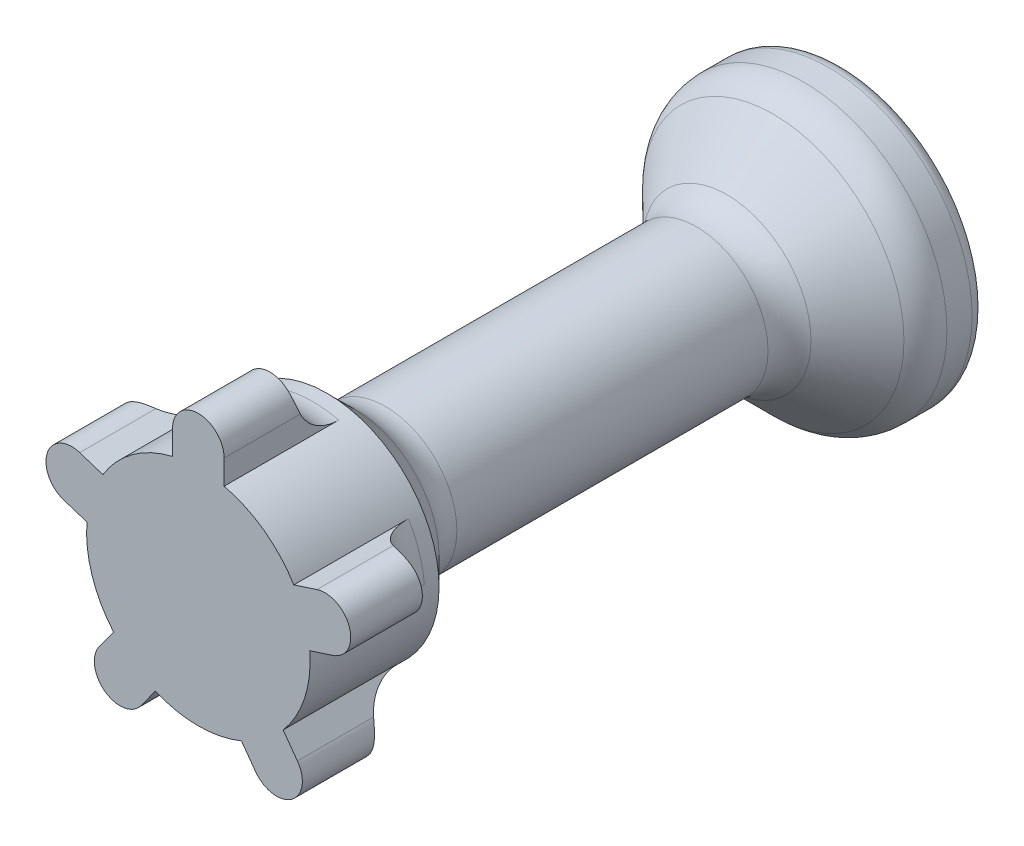
SolidWorks part; units mm, degrees
note: '?' marks a value the reader was unsure of.
ref_plane "Front Plane" through (0, 0, 0) normal (0, 0, 1) x (1, 0, 0)
ref_plane "Top Plane" through (0, 0, 0) normal (0, 1, 0) x (1, 0, 0)
ref_plane "Right Plane" through (0, 0, 0) normal (1, 0, 0) x (0, 0, -1)
ref_axis "Center_Axis" through (0, 0, -88.99) along (0, 0, 1)?
sketch "Sketch1" plane through (0, 0, 0) normal (0, 0, 1) x (1, 0, 0)
  line L0 (11.9266, 1.4716) -> (9.8733, 0.8044)
  line L1 (10.5138, 5.8198) -> (8.4605, 5.1526)
  line L2 (5.0851, -10.8882) -> (3.816, -9.1415)
  line L3 (8.7839, -8.2008) -> (7.5149, -6.4541)
  line L6 (-8.7839, -8.2008) -> (-7.5149, -6.4541)
  line L8 (-2.286, 11.7976) -> (-2.286, 9.6386)
  line L9 (2.286, 11.7976) -> (2.286, 9.6386)
  line L10 (-5.0851, -10.8882) -> (-3.816, -9.1415)
  line L11 (-10.5138, 5.8198) -> (-8.4605, 5.1526)
  line L12 (-11.9266, 1.4716) -> (-9.8733, 0.8044)
  circle A1 centre (0, 0) radius 9.906
  arc A3 (-2.286, 11.7976) -> (2.286, 11.7976) centre (0, 11.7976) cw
  arc A4 (10.5138, 5.8198) -> (11.9266, 1.4716) centre (11.2202, 3.6457) cw
  arc A5 (8.7839, -8.2008) -> (5.0851, -10.8882) centre (6.9345, -9.5445) cw
  arc A6 (-5.0851, -10.8882) -> (-8.7839, -8.2008) centre (-6.9345, -9.5445) cw
  arc A7 (-11.9266, 1.4716) -> (-10.5138, 5.8198) centre (-11.2202, 3.6457) cw
  point P14 (0, 0)
  point P30 (0, 0)
  dimension "D1" = 5
  dimension "D3" = 19.812
  dimension "D5" = 2.159
  dimension "D6" = 4.572
extrude "Boss-Extrude1" add sketch "Sketch1" along normal blind 6.35 contours A7 L12 A1 L11 | A1 | A6 L10 A1 L6 | A5 L3 A1 L2 | A4 L1 A1 L0 | A3 L8 A1 L9
sketch "Sketch2" plane through (0, 0, 0) normal (0, 1, 0) x (1, 0, 0)
  line L0 (0, 0) -> (9.906, 0)
  line L1 (0, 0) -> (0, 50.8)
  line L3 (6.35, 8.636) -> (6.35, 39.37)
  line L5 (0, 50.8) -> (12.7, 50.8)
  line L6 (9.906, 0) -> (9.906, 5.08)
  line L7 (9.906, 5.08) -> (6.35, 8.636)
  line L8 (12.7, 50.8) -> (12.7, 45.72)
  line L9 (12.7, 45.72) -> (6.35, 39.37)
  dimension "D1" = 45
  dimension "D2" = 50.8
  dimension "D3" = 45
  dimension "D4" = 5.08
  dimension "D5" = 6.35
  dimension "D6" = 5.08
  dimension "D7" = 9.906
  dimension "D8" = 12.7
revolve "Revolve1" add sketch "Sketch2" angle 360 about L1
fillet "Fillet1" radius 3.81 5 edges at (6.35, 0, -39.37) (6.35, 0, -8.636) (5.8226, -8.0141, 0) (0, 9.906, 0) (12.7, 0, -45.72)
fillet "Fillet2" radius 1.27 1 edges at (12.7, 0, -50.8)
